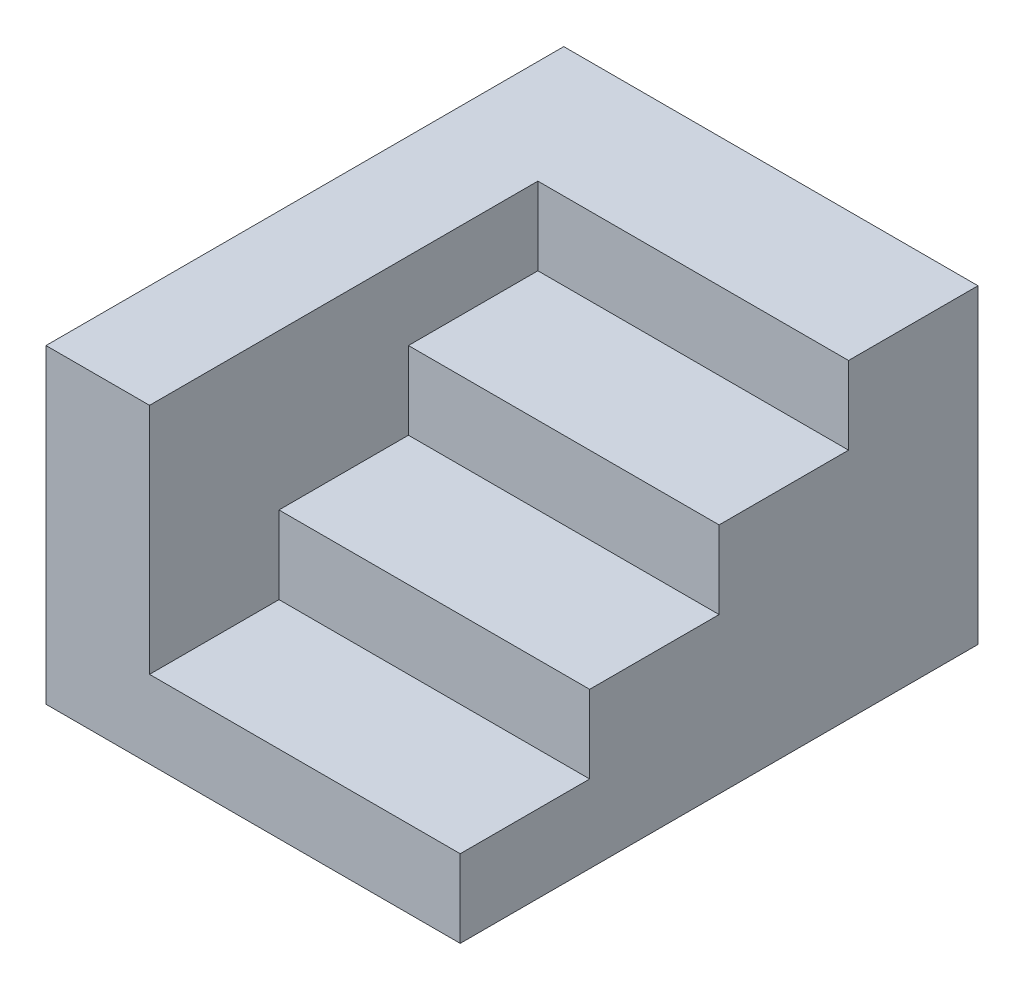
SolidWorks part; units mm, degrees
ref_plane "Front Plane" through (0, 0, 0) normal (0, 0, 1) x (1, 0, 0)
ref_plane "Top Plane" through (0, 0, 0) normal (0, 1, 0) x (1, 0, 0)
ref_plane "Right Plane" through (0, 0, 0) normal (1, 0, 0) x (0, 0, -1)
sketch "Sketch1" plane through (0, 0, 0) normal (1, 0, 0) x (0, 0, -1)
  line L0 (0, 0) -> (0, 15)
  line L1 (0, 0) -> (100, 0)
  line L2 (0, 0) -> (0, 60)
  line L3 (0, 60) -> (100, 60)
  line L4 (100, 0) -> (100, 60)
  line L5 (0, 15) -> (25, 15)
  line L6 (25, 15) -> (25, 30)
  line L7 (25, 30) -> (50, 30)
  line L8 (50, 30) -> (50, 45)
  line L9 (50, 45) -> (75, 45)
  line L10 (75, 45) -> (75, 60)
  dimension "D1" = 60
  dimension "D2" = 100
  dimension "D3" = 25
  dimension "D4" = 15
extrude "Boss-Extrude1" add sketch "Sketch1" along normal blind 20 contours L9 L10 L3 L2 L5 L6 L7 L8 | L10 L9 L8 L7 L6 L5 L0 L1 L4 L3 region at (0, 22.5, -62.5) region at (0, 42.5, -29.1667)
extrude "Boss-Extrude2" add sketch "Sketch1<3>" along normal blind 80 contours L10 L9 L8 L7 L6 L5 L0 L1 L4 L3 region at (0, 22.5, -62.5)
sketch "Sketch1<3>" plane through (0, 0, 0) normal (1, 0, 0) x (0, 0, -1) same geometry as "Sketch1"
